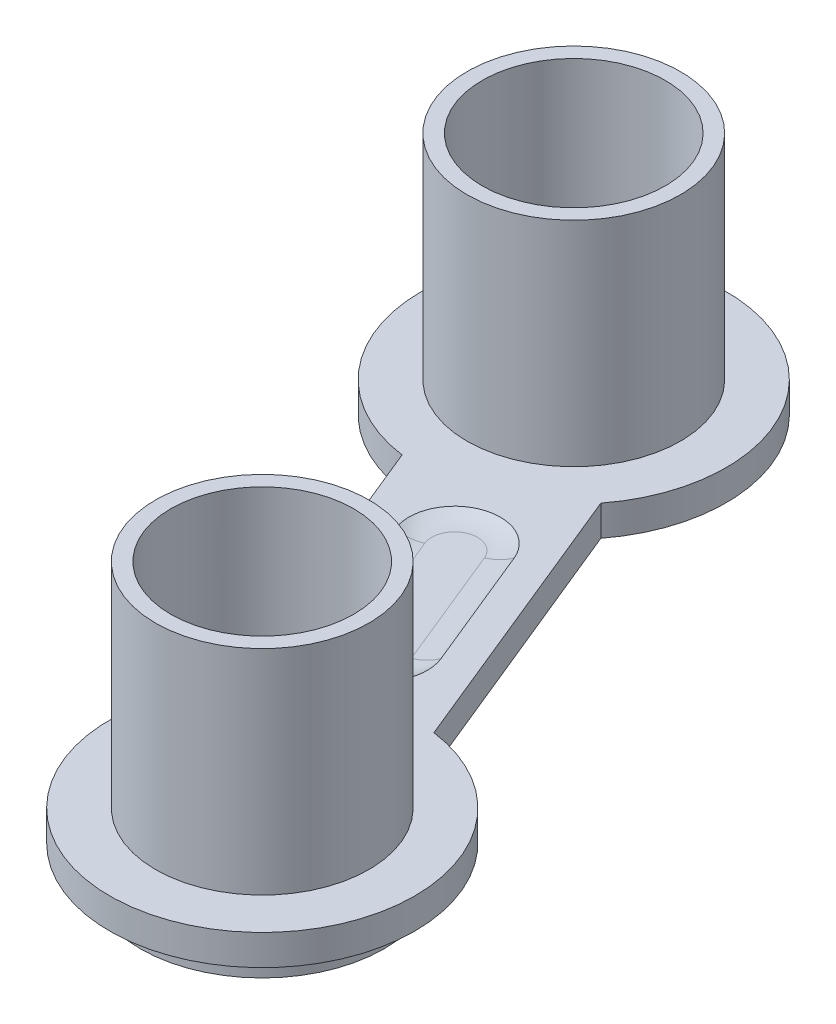
SolidWorks part; units mm, degrees
ref_plane "Alzado" through (0, 0, 0) normal (0, 0, 1) x (1, 0, 0)
ref_plane "Planta" through (0, 0, 0) normal (0, 1, 0) x (1, 0, 0)
ref_plane "Vista lateral" through (0, 0, 0) normal (1, 0, 0) x (0, 0, -1)
sketch "Croquis1" plane through (0, 0, 0) normal (0, 1, 0) x (1, 0, 0)
  line L0 (-54.0473, 15.062) -> (-50.2648, 5.8049)
  line L1 (-57.9994, 18.1248) -> (-50.9412, 0.8509) construction
  line L2 (-58.6758, 13.1708) -> (-54.8934, 3.9137)
  arc A0 (-54.0473, 15.062) -> (-58.6758, 13.1708) centre (-57.9994, 18.1248) ccw
  circle A1 centre (-57.9994, 18.1248) radius 3
  circle A2 centre (-50.9412, 0.8509) radius 5
  circle A3 centre (-50.9412, 0.8509) radius 3
  dimension "D1" = 2.5
  dimension "D3" = 10
  dimension "D4" = 6
  dimension "D7" = 10
  dimension "D8" = 6
  dimension "D2" = 2.5
  dimension "D5" = 10
  dimension "D6" = 10
extrude "Saliente-Extruir1" add sketch "Croquis1" along normal blind 1 contours A2 A3 | A1 A2 L0 A0 L2 region at (-56.3232, 0, -14.0226) region at (-47.2807, 0, -4.0456)
sketch "Croquis2" plane through (0, 1, 0) normal (0, 1, 0) x (1, 0, 0)
  circle A0 centre (-50.9412, 0.8509) radius 3.5
  circle A1 centre (-50.9412, 0.8509) radius 3 construction
  circle A2 centre (-50.9412, 0.8509) radius 3
  circle A3 centre (-57.9994, 18.1248) radius 3.5
  circle A4 centre (-57.9994, 18.1248) radius 3 construction
  circle A5 centre (-57.9994, 18.1248) radius 3
extrude "Saliente-Extruir2" add sketch "Croquis2" along normal blind 7
sketch "Croquis3" plane through (0, 0, 0) normal (0, -1, 0) x (1, 0, 0)
  circle A0 centre (-50.9412, -0.8509) radius 4
  circle A1 centre (-50.9412, -0.8509) radius 3 construction
  circle A2 centre (-50.9412, -0.8509) radius 3
extrude "Saliente-Extruir3" add sketch "Croquis3" along normal blind 1
sketch "Croquis4" plane through (0, 0, 0) normal (0, -1, 0) x (1, 0, 0)
  line L0 (-57.9994, -18.1248) -> (-50.9412, -0.8509) construction
  line L1 (-55.0305, -6.893) -> (-52.2533, -8.0278)
  line L2 (-53.9102, -12.0827) -> (-52.2533, -8.0278)
  line L3 (-56.6873, -10.9479) -> (-55.0305, -6.893)
  line L4 (-56.6873, -10.9479) -> (-53.9102, -12.0827)
  line L5 (-53.6419, -7.4604) -> (-55.2987, -11.5153)
  arc A0 (-52.2533, -8.0278) -> (-55.0305, -6.893) centre (-53.6419, -7.4604) ccw
  arc A1 (-56.6873, -10.9479) -> (-53.9102, -12.0827) centre (-55.2987, -11.5153) ccw
  point P5 (-54.4703, -9.4879)
  point P8 (-53.0818, -10.0552)
  point P11 (-55.8589, -8.9205)
  dimension "D1" = 3
sketch "Croquis5" plane through (-45.6694, 0, 18.6606) normal (-0.9257, 0, 0.3782) x (0.3782, 0, 0.9257)
  line L0 (-34.3861, 0.5) -> (-24.3861, 0.5) construction
  line L1 (-34.3861, 1) -> (-34.3861, 0) construction
  line L2 (-24.3861, 1) -> (-24.3861, 0) construction
ref_plane "Plano1" through (0, 0.5, 0) normal (0, -1, 0) x (0.3782, 0, 0.9257)
extrude "Cortar-Extruir3" cut sketch "Croquis4" against normal blind 0.2 contours L0 L1 A0 | L1 L0 A0 | L1 L5 L4 L2 | L5 L1 L3 L4 | L0 A1 L4 | A1 L0 L4 region at (-53.776, 0, -9.7715) region at (-53.9904, 0, -6.6303) region at (-55.1646, 0, -9.2042) region at (-52.8118, 0, -7.1119) region at (-54.9502, 0, -12.3454) region at (-56.1289, 0, -11.8638)
fillet "Redondeo4" radius 1.5 4 edges at (-55.8661, 0.2, -12.9039) (-53.0818, 0.2, -10.0552) (-53.0745, 0.2, -6.0719) (-55.8589, 0.2, -8.9205)
mirror "Simetría4" about plane through (0, 0.5, 0) normal (0, -1, 0) of "Cortar-Extruir3", "Redondeo4"
